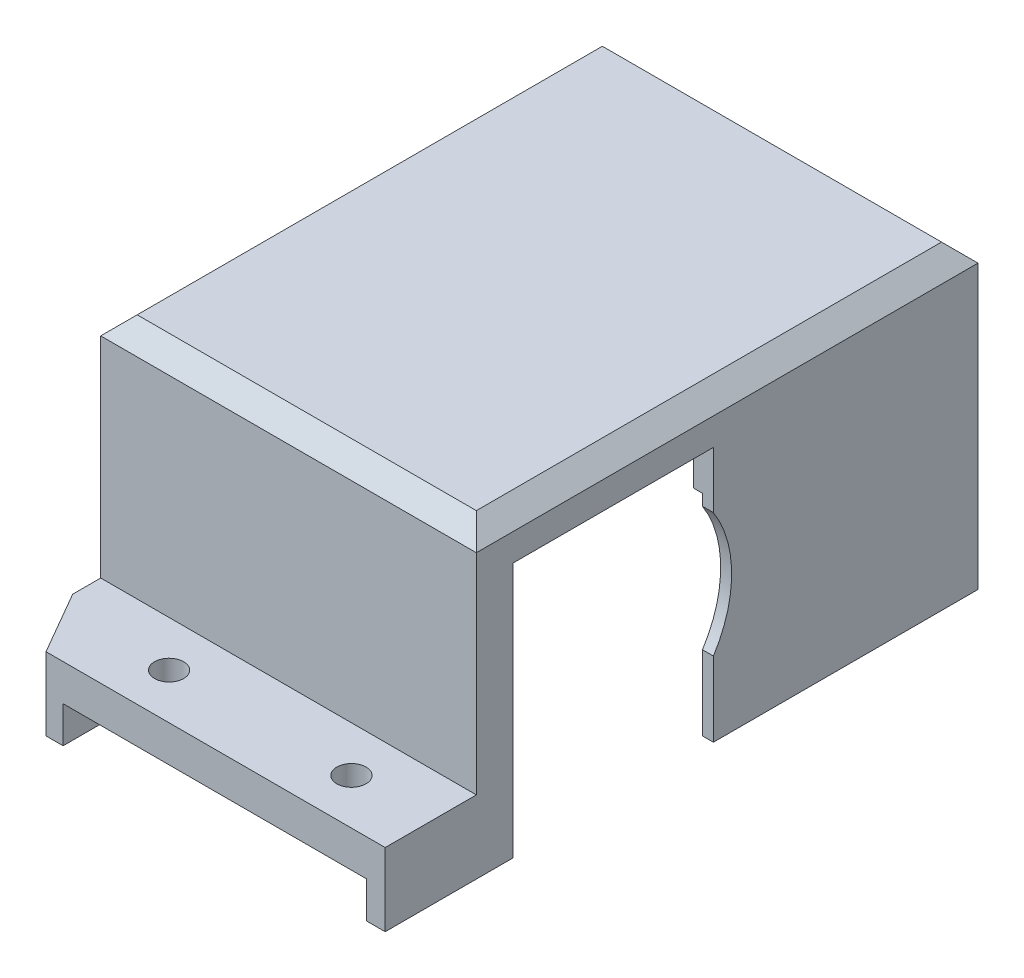
SolidWorks part; units mm, degrees
ref_plane "Front Plane" through (0, 0, 0) normal (0, 0, 1) x (1, 0, 0)
ref_plane "Top Plane" through (0, 0, 0) normal (0, 1, 0) x (1, 0, 0)
ref_plane "Right Plane" through (0, 0, 0) normal (1, 0, 0) x (0, 0, -1)
sketch "Sketch1" plane through (0, 0, 0) normal (0, 1, 0) x (1, 0, 0)
  line L1 (-19.891, 13.2956) -> (19.109, 13.2956)
  line L2 (-19.891, 13.2956) -> (-19.891, -35.9244)
  line L3 (-19.891, -35.9244) -> (19.109, -35.9244)
  line L4 (19.109, 13.2956) -> (19.109, -35.9244)
extrude "Boss-Extrude2" add sketch "Sketch1" along normal blind 30
sketch "Sketch3" plane through (0, 0, 35.9244) normal (0, 0, 1) x (1, 0, 0)
  line L0 (-19.891, 28) -> (19.109, 28)
  line L1 (-19.891, 30) -> (-19.891, 0) construction
  line L2 (19.109, 30) -> (19.109, 0) construction
  line L3 (17.109, 30) -> (17.109, 0) construction
  line L4 (-19.891, 30) -> (19.109, 30) construction
  line L5 (-19.891, 0) -> (19.109, 0) construction
  line L6 (-16.141, 30) -> (-16.141, 0)
  line L7 (-17.891, 30) -> (-17.891, 0)
  line L8 (16.109, 28) -> (16.109, -0.33)
  line L9 (-17.891, 28) -> (17.109, 28)
  line L10 (-17.891, 28) -> (-17.891, 0)
  line L11 (-17.891, 0) -> (17.109, 0)
  line L12 (17.109, 28) -> (17.109, 0)
  line L13 (-17.891, 25.5) -> (-16.141, 25.5)
  line L14 (-17.891, 25.5) -> (-17.891, 5.5)
  line L15 (-17.891, 5.5) -> (-16.141, 5.5)
  line L16 (-16.141, 25.5) -> (-16.141, 5.5)
  line L18 (16.109, 23.05) -> (17.109, 23.05)
  line L19 (16.109, 23.05) -> (16.109, 7.95)
  line L20 (16.109, 7.95) -> (17.109, 7.95)
  line L21 (17.109, 23.05) -> (17.109, 7.95)
  point P22 (-17.016, 5.5)
  point P29 (16.609, 23.05)
  point P30 (16.609, 7.95)
  line M13 (-19.891, 0) -> (19.109, 0)
  dimension "D1" = 3.75
  dimension "D2" = 2
  dimension "D3" = 1.75
  dimension "D4" = 2
  dimension "D5" = 2.5
  dimension "D6" = 5.5
  dimension "D7" = 33.25
  dimension "D8" = 1
  dimension "D9" = 4.95
  dimension "D10" = 7.95
extrude "Cut-Extrude3" cut sketch "Sketch3" against normal blind 47.22 contours L8 L0 L6 M13 | L10 L15 L6 L13 | L8 L20 L12 L18 region at (-0.016, 14, 35.9244) region at (16.609, 15.5, 35.9244) region at (-17.016, 15.5, 35.9244)
sketch "Sketch7" plane through (-19.891, 0, 0) normal (-1, 0, 0) x (0, 0, 1)
  line L0 (8.7044, 30) -> (8.7044, 0)
  line L1 (-13.2956, 30) -> (35.9244, 30) construction
  line L2 (-13.2956, 0) -> (35.9244, 0) construction
  line L3 (-13.2956, 30) -> (-13.2956, 0) construction
  line L4 (-13.2956, 15) -> (35.9244, 15)
  line L5 (35.9244, 30) -> (35.9244, 0) construction
  circle A0 centre (24.3244, 15) radius 12.6
  dimension "D2" = 11.6
  dimension "D1" = 22
extrude "Cut-Extrude4" cut sketch "Sketch7" against normal blind 47.22 contours L2 A0 L4 | L4 A0 L2 region at (-19.891, 2.7564, 24.3244)
sketch "Sketch8" plane through (-19.891, 0, 0) normal (-1, 0, 0) x (0, 0, 1)
  line L0 (-13.2956, 30) -> (35.9244, 30) construction
  line L1 (8.6339, 30) -> (35.9244, 30)
  line L2 (8.6339, 30) -> (8.6339, 0)
  line L3 (8.6339, 0) -> (35.9244, 0)
  line L4 (35.9244, 30) -> (35.9244, 0)
  line L5 (-13.2956, 0) -> (35.9244, 0) construction
  line L6 (35.9244, 10.0807) -> (35.9244, 0) construction
  line L8 (8.6339, 30) -> (17.6339, 30)
  line L9 (8.6339, 30) -> (8.6339, 27)
  line L10 (8.6339, 27) -> (17.6339, 27)
  line L11 (17.6339, 30) -> (17.6339, 27)
  line L12 (8.6339, 0) -> (17.6339, 0)
  line L13 (8.6339, 0) -> (8.6339, 4)
  line L14 (8.6339, 4) -> (17.6339, 4)
  line L15 (17.6339, 0) -> (17.6339, 4)
  line M1 (35.9244, 0) -> (35.9244, 10.0807)
  arc M2 (35.9244, 10.0807) -> (35.9244, 19.9193) centre (24.3244, 15) cw
  line M3 (35.9244, 19.9193) -> (35.9244, 30)
  line M4 (35.9244, 30) -> (-13.2956, 30)
extrude "Cut-Extrude5" cut sketch "Sketch8" against normal blind 3.75 contours L15 L3 L11 L10 L2 L14 M1 M2 M3 M4 region at (-19.891, 29.5944, 26.7792)
sketch "Sketch9" plane through (19.109, 0, 0) normal (1, 0, 0) x (0, 0, -1)
  line L0 (-35.9244, 0) -> (13.2956, 0) construction
  line L1 (-35.9244, 30) -> (-13.7244, 30)
  line L2 (-35.9244, 30) -> (-35.9244, 0)
  line L3 (-35.9244, 0) -> (-13.7244, 0)
  line L4 (-13.7244, 30) -> (-13.7244, 0)
  dimension "D1" = 22.2
extrude "Cut-Extrude7" cut sketch "Sketch9" against normal through all
sketch "Sketch11" plane through (0, 0, 13.7244) normal (0, 0, 1) x (1, 0, 0)
  line L0 (-18.891, 30) -> (-18.891, 0)
  line L1 (19.109, 0) -> (-19.891, 0)
  line L2 (19.109, 0) -> (19.109, 30)
  line L3 (19.109, 30) -> (-19.891, 30)
  line L4 (-19.891, 0) -> (-19.891, 30)
  line L5 (18.309, 30) -> (18.309, 0)
  line M9 (19.109, 0) -> (19.109, 8.1882)
  line M10 (19.109, 8.1882) -> (17.109, 8.1882)
  dimension "D1" = 1
  dimension "D2" = 0.8
extrude "Cut-Extrude8" cut sketch "Sketch11" against normal through all contours L3 L5 L2 M10 | L5 L1 M10 M9 region at (18.709, 19.0941, 13.7244) region at (18.709, 4.0941, 13.7244)
sketch "Sketch12" plane through (18.309, 0, 0) normal (1, 0, 0) x (0, 0, -1)
  line L1 (13.2956, 0) -> (-9.7044, 0)
  line L2 (13.2956, 0) -> (13.2956, 2.5)
  line L3 (13.2956, 2.5) -> (-9.7044, 2.5)
  line L4 (-9.7044, 0) -> (-9.7044, 2.5)
extrude "Boss-Extrude3" add sketch "Sketch12" along normal blind 3
sketch "Sketch13" plane through (-19.891, 0, 0) normal (-1, 0, 0) x (0, 0, 1)
  line L1 (-13.2956, 0) -> (9.7044, 0)
  line L2 (-13.2956, 0) -> (-13.2956, 2.5)
  line L3 (-13.2956, 2.5) -> (9.7044, 2.5)
  line L4 (9.7044, 0) -> (9.7044, 2.5)
extrude "Boss-Extrude4" add sketch "Sketch13" along normal blind 3
sketch "Sketch14" plane through (-16.141, 0, 0) normal (1, 0, 0) x (0, 0, -1)
  line L0 (-13.7244, 0) -> (-13.7244, 8.1882) construction
  line L1 (-13.7244, 3) -> (13.2956, 3)
  line L2 (-13.7244, 3) -> (-13.7244, 0)
  line L3 (-13.7244, 0) -> (13.2956, 0)
  line L4 (13.2956, 3) -> (13.2956, 0)
extrude "Boss-Extrude5" add sketch "Sketch14" along normal up to next
sketch "Sketch15" plane through (0, 0, 13.7244) normal (0, 0, 1) x (1, 0, 0)
  line L1 (-19.891, 0) -> (18.309, 0) construction
  line L2 (16.109, 3) -> (-16.141, 3) construction
  line L5 (-15.141, 3) -> (-15.141, 0)
  line L6 (-15.141, 0) -> (15.109, 0)
  line L7 (15.109, 0) -> (15.109, 3)
  line L8 (-15.141, 3) -> (15.109, 3)
extrude "Cut-Extrude9" cut sketch "Sketch15" against normal up to surface (25.02 mm away) up to face at (-0.141, 15.5, -11.2956)
sketch "Sketch16" plane through (0, 0, -11.2956) normal (0, 0, 1) x (1, 0, 0)
  line L1 (-15.141, 0) -> (15.109, 0)
  line L2 (-15.141, 0) -> (-15.141, 3)
  line L3 (-15.141, 3) -> (15.109, 3)
  line L4 (15.109, 0) -> (15.109, 3)
extrude "Cut-Extrude10" cut sketch "Sketch16" against normal through all
sketch "Sketch23" plane through (-19.891, 0, 0) normal (-1, 0, 0) x (0, 0, 1)
  line L0 (-13.2956, 2.5) -> (-13.2956, 30)
  line L1 (-13.2956, 30) -> (13.7244, 30)
  line L2 (13.7244, 30) -> (13.7244, 27)
  line L3 (13.7244, 27) -> (8.6339, 27)
  line L4 (8.6339, 27) -> (8.6339, 4)
  line L5 (8.6339, 4) -> (13.7244, 4)
  line L6 (13.7244, 4) -> (13.7244, 0)
  line L7 (13.7244, 0) -> (9.7044, 0)
  line L8 (9.7044, 0) -> (9.7044, 2.5)
  line L9 (9.7044, 2.5) -> (-13.2956, 2.5)
sketch "Sketch24" plane through (-22.891, 0, 0) normal (-1, 0, 0) x (0, 0, 1)
  line L0 (-13.2956, 2.5) -> (9.7044, 2.5)
  line L1 (9.7044, 2.5) -> (9.7044, 0)
  line L2 (9.7044, 0) -> (-13.2956, 0)
  line L3 (-13.2956, 0) -> (-13.2956, 2.5)
extrude "Boss-Extrude8" add sketch "Sketch24" along normal blind 6
sketch "Sketch25" plane through (-19.891, 0, 0) normal (-1, 0, 0) x (0, 0, 1)
  line L0 (-13.2956, 30) -> (13.7244, 30)
  line L1 (13.7244, 30) -> (13.7244, 27)
  line L2 (13.7244, 27) -> (8.6339, 27)
  line L3 (8.6339, 27) -> (8.6339, 4)
  line L4 (8.6339, 4) -> (13.7244, 4)
  line L5 (13.7244, 4) -> (13.7244, 0)
  line L6 (13.7244, 0) -> (9.7044, 0)
  line L7 (9.7044, 0) -> (9.7044, 2.5)
  line L8 (9.7044, 2.5) -> (-13.2956, 2.5)
  line L9 (-13.2956, 2.5) -> (-13.2956, 30)
extrude "Boss-Extrude9" add sketch "Sketch25" along normal blind 3
sketch "Sketch26" plane through (0, 30, 0) normal (0, 1, 0) x (1, 0, 0)
  line L1 (-22.891, 13.2956) -> (18.309, 13.2956)
  line L2 (-22.891, 13.2956) -> (-22.891, -13.7244)
  line L3 (-22.891, -13.7244) -> (18.309, -13.7244)
  line L4 (18.309, 13.2956) -> (18.309, -13.7244)
extrude "Boss-Extrude10" add sketch "Sketch26" along normal blind 3
sketch "Sketch29" plane through (0, 25.5, 0) normal (0, -1, 0) x (1, 0, 0)
  line L1 (-17.891, -11.2956) -> (-13.6266, -11.2956)
  line L2 (-17.891, -11.2956) -> (-17.891, 15.1522)
  line L3 (-17.891, 15.1522) -> (-13.6266, 15.1522)
  line L4 (-13.6266, -11.2956) -> (-13.6266, 15.1522)
extrude "Cut-Extrude14" cut sketch "Sketch29" along normal through all
sketch "Sketch30" plane through (0, 23.05, 0) normal (0, -1, 0) x (-1, 0, 0)
  line L1 (-17.109, 11.2956) -> (-13.1276, 11.2956)
  line L2 (-17.109, 11.2956) -> (-17.109, -22.36)
  line L3 (-17.109, -22.36) -> (-13.1276, -22.36)
  line L4 (-13.1276, 11.2956) -> (-13.1276, -22.36)
extrude "Cut-Extrude15" cut sketch "Sketch30" along normal through all
sketch "Sketch34" plane through (0, 0, -13.2956) normal (0, 0, -1) x (-1, 0, 0)
  line L0 (-18.309, 33) -> (-18.309, 2.5)
  line L1 (-18.309, 2.5) -> (-21.309, 2.5)
  line L2 (-21.309, 2.5) -> (-21.309, 0)
  line L3 (-21.309, 0) -> (28.891, 0)
  line L4 (28.891, 0) -> (28.891, 2.5)
  line L5 (28.891, 2.5) -> (22.891, 2.5)
  line L6 (22.891, 2.5) -> (22.891, 33)
  line L7 (22.891, 33) -> (-18.309, 33)
extrude "Boss-Extrude15" add sketch "Sketch34" against normal up to surface (2 mm away) up to face at (-0.141, 13.2583, -11.2956)
sketch "Sketch35" plane through (0, 0, -13.2956) normal (0, 0, -1) x (-1, 0, 0)
  line L0 (-18.309, 33) -> (-18.309, 2.5)
  line L1 (-18.309, 2.5) -> (-21.309, 2.5)
  line L2 (-21.309, 2.5) -> (-21.309, 0)
  line L3 (-21.309, 0) -> (-21.309, 2.5) construction
  line L4 (-21.309, 0) -> (28.891, 0)
  line L5 (28.891, 0) -> (28.891, 2.5)
  line L6 (28.891, 2.5) -> (22.891, 2.5)
  line L7 (22.891, 2.5) -> (22.891, 33)
  line L8 (22.891, 33) -> (-18.309, 33)
extrude "Boss-Extrude16" add sketch "Sketch35" along normal blind 2
sketch "Sketch36" plane through (0, 0, 13.7244) normal (0, 0, 1) x (1, 0, 0)
  line L0 (18.309, 33) -> (18.309, 21.8118) construction
  line L1 (-22.891, 33) -> (18.309, 33)
  line L2 (-22.891, 33) -> (-22.891, 28.0065)
  line L3 (-22.891, 28.0065) -> (18.309, 28.0065)
  line L4 (18.309, 33) -> (18.309, 28.0065)
extrude "Boss-Extrude17" add sketch "Sketch36" along normal blind 26
sketch "Sketch37" plane through (0, 28.0065, 0) normal (0, -1, 0) x (-1, 0, 0)
  line L0 (-18.309, -39.7244) -> (-18.309, -13.7244) construction
  line L1 (22.891, -39.7244) -> (-18.309, -39.7244)
  line L2 (22.891, -39.7244) -> (22.891, -34.7244)
  line L3 (22.891, -34.7244) -> (-18.309, -34.7244)
  line L4 (-18.309, -39.7244) -> (-18.309, -34.7244)
extrude "Boss-Extrude18" add sketch "Sketch37" along normal up to surface (28.0065 mm away) up to face at (-2.1577, 0, 3.3777)
sketch "Sketch38" plane through (0, 0, 39.7244) normal (0, 0, 1) x (1, 0, 0)
  line L0 (18.309, 0) -> (18.309, 33) construction
  line L1 (-22.891, 0) -> (18.309, 0)
  line L2 (-22.891, 0) -> (-22.891, 5)
  line L3 (-22.891, 5) -> (18.309, 5)
  line L4 (18.309, 0) -> (18.309, 5)
extrude "Boss-Extrude19" add sketch "Sketch38" along normal blind 20
sketch "Sketch39" plane through (0, 5, 0) normal (0, 1, 0) x (1, 0, 0)
  line L0 (18.309, -59.7244) -> (-22.891, -59.7244) construction
  line L1 (-22.891, -59.7244) -> (-4.0386, -65.4643)
  line L2 (18.309, -59.7244) -> (-0.5435, -65.4643)
  line L3 (-22.891, -59.7244) -> (-8.291, -59.7244)
  line L4 (-8.291, -59.7244) -> (18.309, -59.7244)
  circle A0 centre (-2.291, -59.7244) radius 6
  circle A1 centre (-2.291, -59.7244) radius 2
  line M6 (-22.891, -59.7244) -> (18.309, -59.7244)
extrude "Boss-Extrude21" add sketch "Sketch39" against normal up to surface (5 mm away) contours A0 L1 M6 | A1 A0 M6 | A0 L2 L4 region at (-12.5637, 5, 61.4411) region at (-2.291, 5, 62.4831) region at (7.9816, 5, 61.4411) up to face at (-2.291, 0, 47.2244)
sketch "Sketch40" plane through (0, 5, 0) normal (0, 1, 0) x (1, 0, 0)
  line L0 (-0.291, -59.7244) -> (-4.291, -59.7244) construction
  circle A0 centre (-2.291, -59.7244) radius 2
extrude "Cut-Extrude16" cut sketch "Sketch40" against normal through all
fillet "Fillet1" radius 2 6 edges at (18.309, 33, 12.2144) (-2.291, 33, -15.2956) (-22.891, 33, 12.2144) (-2.291, 33, 39.7244) (-22.891, 2.5, 59.7244) (18.309, 2.5, 59.7244) profile chamfer
sketch "Sketch41" plane through (0, 0, -15.2956) normal (0, 0, -1) x (-1, 0, 0)
  line L1 (2.291, 5) -> (17.291, 5)
  line L2 (17.291, 5) -> (17.291, 0)
  line L3 (2.291, 5) -> (-12.709, 5)
  line L5 (-12.709, 5) -> (-12.709, 0)
  line L6 (-21.309, 0) -> (28.891, 0) construction
  line L7 (-12.709, 0) -> (2.291, 0)
  line L9 (2.291, 0) -> (17.291, 0)
  line L10 (-12.709, 0) -> (2.291, 0)
  line M6 (-21.309, 0) -> (28.891, 0)
extrude "Boss-Extrude22" add sketch "Sketch41" along normal blind 10 contours L3 L5 L2 L1 M6 region at (-2.291, 2.5, -15.2956)
sketch "Sketch42" plane through (0, 0, -11.2956) normal (0, 0, 1) x (1, 0, 0)
  line L0 (-0.391, 0) -> (-0.391, 36.4349) construction
  line L1 (-17.891, 0) -> (17.109, 0) construction
  line L2 (-17.016, 0) -> (16.234, 0)
  line L4 (16.234, 0) -> (16.234, 4)
  line L5 (16.234, 4) -> (-17.016, 4)
  line L6 (-17.016, 0) -> (-17.016, 4)
  line L7 (-0.391, 0) -> (-17.016, 4) construction
  line L8 (16.234, 4) -> (-0.391, 0) construction
extrude "Cut-Extrude17" cut sketch "Sketch42" against normal through all
sketch "Sketch43" plane through (0, 0, -25.2956) normal (0, 0, -1) x (-1, 0, 0)
  line L1 (-12.709, 5) -> (17.291, 5)
  line L2 (-12.709, 5) -> (-12.709, 0)
  line L3 (-12.709, 0) -> (17.291, 0)
  line L4 (17.291, 5) -> (17.291, 0)
extrude "Cut-Extrude19" cut sketch "Sketch43" against normal up to surface (10 mm away) up to face at (-0.0732, 6.4286, -15.2956)
sketch "Sketch44" plane through (0, 0, -15.2956) normal (0, 0, -1) x (-1, 0, 0)
  line L0 (17.016, 4) -> (-16.234, 4) construction
  line L1 (-9.609, 8.5) -> (10.391, 8.5)
  line L2 (-9.609, 8.5) -> (-9.609, 4)
  line L4 (10.391, 8.5) -> (10.391, 4)
  line L5 (-9.609, 8.5) -> (0.391, 4) construction
  line L6 (0.391, 4) -> (10.391, 8.5) construction
  line L7 (-9.609, 4) -> (10.391, 4)
  point P0 (0.391, 4)
extrude "Boss-Extrude23" add sketch "Sketch44" along normal blind 6 contours L1 L4 L7 L2
sketch "Sketch45" plane through (0, 0, 0) normal (0, -1, 0) x (-1, 0, 0)
  line L0 (-18.309, -58.2427) -> (-18.309, -34.7244) construction
  line L1 (22.891, -34.7244) -> (-18.309, -34.7244)
  line L2 (22.891, -34.7244) -> (22.891, -49.7244)
  line L3 (22.891, -49.7244) -> (-18.309, -49.7244)
  line L4 (-18.309, -34.7244) -> (-18.309, -49.7244)
extrude "Cut-Extrude20" cut sketch "Sketch45" against normal blind 3
sketch "Sketch46" plane through (0, 0, 0) normal (0, -1, 0) x (-1, 0, 0)
  line L1 (22.891, -49.7244) -> (-18.309, -49.7244)
  line L2 (22.891, -49.7244) -> (22.891, -65.9315)
  line L3 (22.891, -65.9315) -> (-18.309, -65.9315)
  line L4 (-18.309, -49.7244) -> (-18.309, -65.9315)
extrude "Cut-Extrude21" cut sketch "Sketch46" against normal through all
sketch "Sketch47" plane through (0, 5, 0) normal (0, 1, 0) x (1, 0, 0)
  line L1 (-22.891, -39.7244) -> (18.309, -39.7244)
  line L2 (-22.891, -39.7244) -> (-22.891, -49.7244)
  line L3 (-22.891, -49.7244) -> (18.309, -49.7244)
  line L4 (18.309, -39.7244) -> (18.309, -49.7244)
extrude "Boss-Extrude24" add sketch "Sketch47" along normal blind 3
sketch "Sketch48" plane through (0, 2.5, 0) normal (0, 1, 0) x (1, 0, 0)
  line L1 (-28.891, 15.2956) -> (-22.891, 15.2956)
  line L2 (-28.891, 15.2956) -> (-28.891, -9.7044)
  line L3 (-28.891, -9.7044) -> (-22.891, -9.7044)
  line L4 (-22.891, 15.2956) -> (-22.891, -9.7044)
  line L5 (18.309, 15.2956) -> (21.309, 15.2956)
  line L6 (18.309, 15.2956) -> (18.309, -9.7044)
  line L7 (18.309, -9.7044) -> (21.309, -9.7044)
  line L8 (21.309, 15.2956) -> (21.309, -9.7044)
extrude "Cut-Extrude22" cut sketch "Sketch48" against normal through all
sketch "Sketch50" plane through (0, 0, 34.7244) normal (0, 0, -1) x (-1, 0, 0)
  line L0 (17.016, 4) -> (17.016, 0) construction
  line L1 (-16.234, 4) -> (17.016, 4)
  line L2 (-16.234, 4) -> (-16.234, 3)
  line L3 (-16.234, 3) -> (17.016, 3)
  line L4 (17.016, 4) -> (17.016, 3)
  line L5 (22.891, 3) -> (-18.309, 3) construction
extrude "Cut-Extrude23" cut sketch "Sketch50" against normal through all
sketch "Sketch51" plane through (0, 3, 0) normal (0, -1, 0) x (1, 0, 0)
  line L0 (-17.016, 49.7244) -> (-17.016, 34.7244) construction
  line L1 (-22.891, 49.7244) -> (-17.016, 49.7244)
  line L2 (-22.891, 49.7244) -> (-22.891, 34.7244)
  line L3 (-22.891, 34.7244) -> (-17.016, 34.7244)
  line L4 (-17.016, 49.7244) -> (-17.016, 34.7244)
  line L5 (-17.016, 49.7244) -> (-17.016, 34.7244) construction
  line L7 (16.234, 49.7244) -> (18.309, 49.7244)
  line L8 (16.234, 49.7244) -> (16.234, 34.7244)
  line L9 (16.234, 34.7244) -> (18.309, 34.7244)
  line L10 (18.309, 49.7244) -> (18.309, 34.7244)
extrude "Boss-Extrude25" add sketch "Sketch51" along normal blind 3
sketch "Sketch52" plane through (0, 4, 0) normal (0, -1, 0) x (-1, 0, 0)
  line L5 (17.016, -49.7244) -> (-16.234, -49.7244) construction
  line L6 (10.391, 21.2956) -> (-9.609, 21.2956)
  line L8 (10.391, -49.7244) -> (-9.609, -49.7244)
  line L11 (10.391, -49.7244) -> (-9.609, -49.7244)
  line L12 (10.391, -49.7244) -> (10.391, -44.7244)
  line L13 (10.391, -44.7244) -> (-9.609, -44.7244)
  line L14 (-9.609, -49.7244) -> (-9.609, -44.7244)
  circle A2 centre (10.391, -44.7244) radius 1.6
  circle A3 centre (-9.609, -44.7244) radius 1.6
extrude "Cut-Extrude24" cut sketch "Sketch52" against normal through all and the other way blind 10 contours L12 A2 L13 | L13 A3 L14 | L14 A3 L13 | L13 A2 L12 region at (-9.712, 4, 45.4035) region at (-10.6174, 4, 44.498) region at (9.8353, 4, 44.498) region at (8.9299, 4, 45.4035)
sketch "Sketch54" plane through (0, 0, 0) normal (0, -1, 0) x (-1, 0, 0)
  line L0 (-18.309, -34.7244) -> (-18.309, -49.7244) construction
  line L1 (22.891, -34.7244) -> (-18.309, -34.7244)
  line L2 (22.891, -34.7244) -> (22.891, -35.7244)
  line L3 (22.891, -35.7244) -> (-18.309, -35.7244)
  line L4 (-18.309, -34.7244) -> (-18.309, -35.7244)
extrude "Cut-Extrude25" cut sketch "Sketch54" against normal up to surface (28.0065 mm away) up to face at (-2.291, 28.0065, 24.2244)
chamfer "Chamfer1" distance 2 angle 45 1 edges at (-22.891, 15.5, -15.2956)
sketch "Sketch55" plane through (0, 8, 0) normal (0, 1, 0) x (1, 0, 0)
  line L1 (-22.891, -42.7962) -> (-22.891, -49.7244)
  line L3 (-18.891, -49.7244) -> (-22.891, -42.7962)
  line L5 (-22.891, -49.7244) -> (-18.891, -49.7244)
  line L7 (-22.891, -49.7244) -> (18.309, -49.7244) construction
  line L8 (-22.891, -39.7244) -> (-22.891, -49.7244) construction
  dimension "D1" = 8
  dimension "D2" = 60
extrude "Cut-Extrude28" cut sketch "Sketch55" against normal through all
